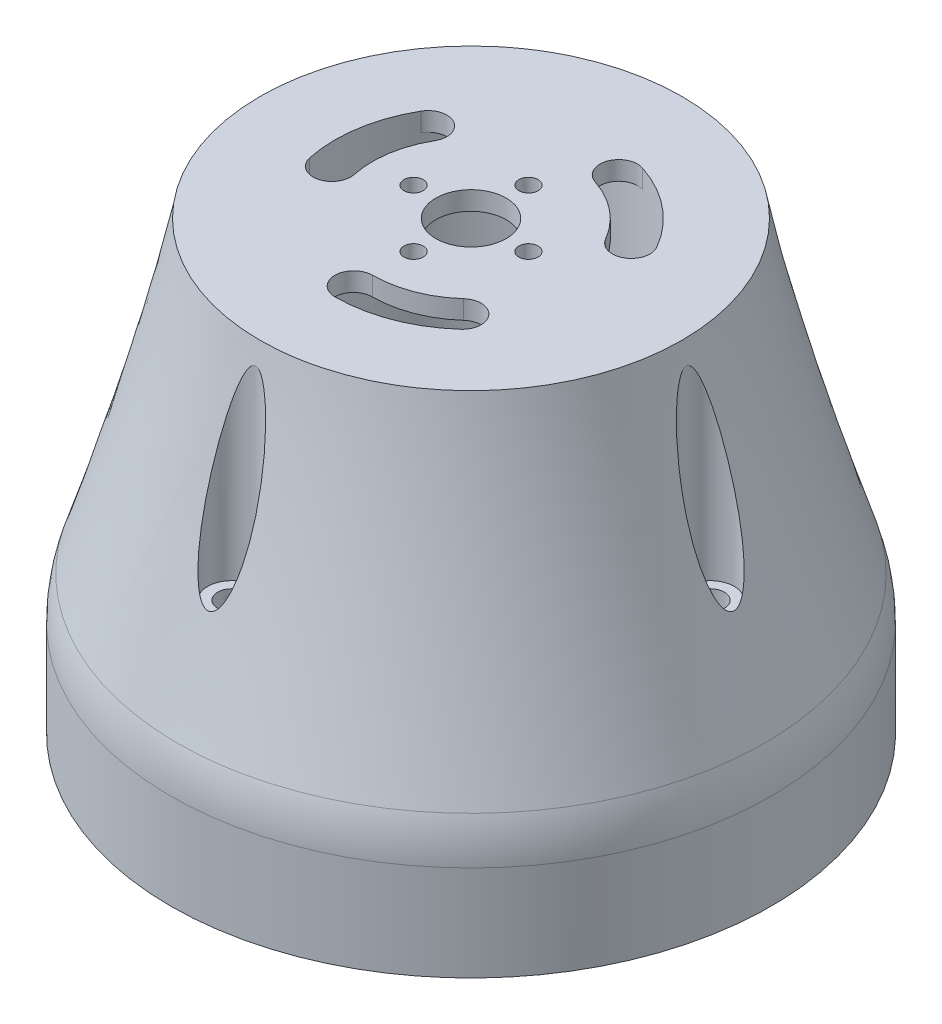
SolidWorks part; units mm, degrees
ref_plane "Front Plane" through (0, 0, 0) normal (0, 0, 1) x (1, 0, 0)
ref_plane "Top Plane" through (0, 0, 0) normal (0, 1, 0) x (1, 0, 0)
ref_plane "Right Plane" through (0, 0, 0) normal (1, 0, 0) x (0, 0, -1)
sketch "Sketch3" plane through (0, 0, 0) normal (0, 1, 0) x (1, 0, 0)
  circle A0 centre (0, 0) radius 64
  dimension "D1" = 128
extrude "Boss-Extrude1" add sketch "Sketch3" along normal blind 15
ref_plane "Plane1" through (0, 85, 0) normal (0, 1, 0) x (1, 0, 0)
sketch "Sketch4" plane through (0, 85, 0) normal (0, 1, 0) x (1, 0, 0)
  circle A0 centre (0, 0) radius 45
  dimension "D1" = 90
sketch "Sketch5" plane through (0, 15, 0) normal (0, 1, 0) x (1, 0, 0)
  circle A1 centre (0, 0) radius 64
  circle A2 centre (0, 0) radius 64
  dimension "D1" = 0
loft "Loft1" add profiles "Sketch5", "Sketch4" connector at (-2.5729, 15, 63.9483) connector at (15.8799, 85, 42.105)
fillet "Fillet1" radius 30 1 edges at (0, 15, 64) type face fillet first side face at (0, 15, 64) second side face at (0, 15, 64)
sketch "Sketch6" plane through (0, 85, 0) normal (0, 1, 0) x (1, 0, 0)
  circle A0 centre (0, 0) radius 51 construction
  circle A1 centre (0, 51) radius 3
  circle A2 centre (51, 0) radius 3
  circle A3 centre (0, -51) radius 3
  circle A4 centre (-51, 0) radius 3
  point P14 (0, 0)
  dimension "D1" = 102
  dimension "D2" = 6
  dimension "D3" = 4
extrude "Cut-Extrude1" cut sketch "Sketch6" against normal blind 85
sketch "Sketch8" plane through (0, 85, 0) normal (0, 1, 0) x (1, 0, 0)
  circle A0 centre (-51, 0) radius 5.11
  circle A1 centre (0, 51) radius 5.11
  circle A2 centre (51, 0) radius 5.11
  circle A3 centre (0, -51) radius 5.11
  point P12 (0, 0)
  dimension "D1" = 10.22
  dimension "D2" = 4
extrude "Cut-Extrude3" cut sketch "Sketch8" against normal blind 45
sketch "Sketch9" plane through (0, 0, 0) normal (0, -1, 0) x (1, 0, 0)
  arc A0 (-16.4684, 53.5238) -> (-53.5238, 16.4684) centre (0, 0) ccw
  arc A1 (-7.1314, 48.6777) -> (7.1314, 48.6777) centre (0, 51) ccw
  arc A5 (-7.1314, 48.6777) -> (-16.4684, 53.5238) centre (-14.2628, 46.3554) ccw
  arc A6 (16.4684, 53.5238) -> (7.1314, 48.6777) centre (14.2628, 46.3554) ccw
  arc A7 (48.6777, 7.1314) -> (53.5238, 16.4684) centre (46.3554, 14.2628) ccw
  arc A8 (48.6777, 7.1314) -> (48.6777, -7.1314) centre (51, 0) ccw
  arc A9 (53.5238, -16.4684) -> (48.6777, -7.1314) centre (46.3554, -14.2628) ccw
  arc A10 (7.1314, -48.6777) -> (16.4684, -53.5238) centre (14.2628, -46.3554) ccw
  arc A11 (7.1314, -48.6777) -> (-7.1314, -48.6777) centre (0, -51) ccw
  arc A12 (-16.4684, -53.5238) -> (-7.1314, -48.6777) centre (-14.2628, -46.3554) ccw
  arc A13 (-48.6777, -7.1314) -> (-53.5238, -16.4684) centre (-46.3554, -14.2628) ccw
  arc A14 (-48.6777, -7.1314) -> (-48.6777, 7.1314) centre (-51, 0) ccw
  arc A15 (-53.5238, 16.4684) -> (-48.6777, 7.1314) centre (-46.3554, 14.2628) ccw
  arc A16 (53.5238, 16.4684) -> (16.4684, 53.5238) centre (0, 0) ccw
  arc A17 (16.4684, -53.5238) -> (53.5238, -16.4684) centre (0, 0) ccw
  arc A18 (-53.5238, -16.4684) -> (-16.4684, -53.5238) centre (0, 0) ccw
  point P15 (0, 0)
  point P35 (0, 0)
  dimension "D1" = 112
  dimension "D2" = 15
  dimension "D3" = 4
  dimension "D4" = 15
  dimension "D5" = 15
extrude "Cut-Extrude4" cut sketch "Sketch9" against normal blind 12
sketch "Sketch17" plane through (0, 12, 0) normal (0, -1, 0) x (1, 0, 0)
  circle A0 centre (0, 0) radius 29
  dimension "D1" = 58
extrude "Cut-Extrude10" cut sketch "Sketch17" against normal blind 69
sketch "Sketch19" plane through (0, 0, 0) normal (0, -1, 0) x (1, 0, 0)
  arc A0 (16.4684, -53.5238) -> (53.5238, -16.4684) centre (0, 0) ccw construction
  circle A1 centre (0, 0) radius 64
  circle A2 centre (0, 0) radius 64
  arc A3 (53.5238, -16.4684) -> (48.6777, -7.1314) centre (46.3554, -14.2628) ccw construction
  arc A4 (48.6777, 7.1314) -> (48.6777, -7.1314) centre (51, 0) ccw construction
  arc A5 (48.6777, 7.1314) -> (53.5238, 16.4684) centre (46.3554, 14.2628) ccw construction
  arc A6 (53.5238, 16.4684) -> (16.4684, 53.5238) centre (0, 0) ccw construction
  arc A7 (-7.1314, 48.6777) -> (7.1314, 48.6777) centre (0, 51) ccw construction
  arc A8 (-7.1314, 48.6777) -> (-16.4684, 53.5238) centre (-14.2628, 46.3554) ccw construction
  arc A9 (16.4684, -53.5238) -> (53.5238, -16.4684) centre (0, 0) ccw
  arc A10 (53.5238, -16.4684) -> (48.6777, -7.1314) centre (46.3554, -14.2628) ccw
  arc A11 (48.6777, 7.1314) -> (48.6777, -7.1314) centre (51, 0) ccw
  arc A12 (48.6777, 7.1314) -> (53.5238, 16.4684) centre (46.3554, 14.2628) ccw
  arc A13 (53.5238, 16.4684) -> (16.4684, 53.5238) centre (0, 0) ccw
  arc A14 (-7.1314, 48.6777) -> (7.1314, 48.6777) centre (0, 51) ccw
  arc A15 (-7.1314, 48.6777) -> (-16.4684, 53.5238) centre (-14.2628, 46.3554) ccw
  arc A18 (16.4684, 53.5238) -> (7.1314, 48.6777) centre (14.2628, 46.3554) ccw
  arc A19 (-7.1314, 48.6777) -> (7.1314, 48.6777) centre (0, 51) ccw
  arc A20 (-7.1314, 48.6777) -> (-16.4684, 53.5238) centre (-14.2628, 46.3554) ccw
  arc A21 (-16.4684, 53.5238) -> (-53.5238, 16.4684) centre (0, 0) ccw
  arc A22 (-53.5238, 16.4684) -> (-48.6777, 7.1314) centre (-46.3554, 14.2628) ccw
  arc A23 (-48.6777, -7.1314) -> (-48.6777, 7.1314) centre (-51, 0) ccw
  arc A24 (-48.6777, -7.1314) -> (-53.5238, -16.4684) centre (-46.3554, -14.2628) ccw
  arc A25 (-53.5238, -16.4684) -> (-16.4684, -53.5238) centre (0, 0) ccw
  arc A26 (-16.4684, -53.5238) -> (-7.1314, -48.6777) centre (-14.2628, -46.3554) ccw
  arc A27 (7.1314, -48.6777) -> (-7.1314, -48.6777) centre (0, -51) ccw
  arc A28 (7.1314, -48.6777) -> (16.4684, -53.5238) centre (14.2628, -46.3554) ccw
  arc A29 (16.4684, -53.5238) -> (53.5238, -16.4684) centre (0, 0) ccw
  arc A30 (53.5238, -16.4684) -> (48.6777, -7.1314) centre (46.3554, -14.2628) ccw
  arc A31 (48.6777, 7.1314) -> (48.6777, -7.1314) centre (51, 0) ccw
  arc A32 (48.6777, 7.1314) -> (53.5238, 16.4684) centre (46.3554, 14.2628) ccw
  arc A33 (53.5238, 16.4684) -> (16.4684, 53.5238) centre (0, 0) ccw
  arc A34 (16.4684, 53.5238) -> (7.1314, 48.6777) centre (14.2628, 46.3554) ccw
  arc A35 (-7.1314, 48.6777) -> (7.1314, 48.6777) centre (0, 51) ccw
  arc A36 (-7.1314, 48.6777) -> (-16.4684, 53.5238) centre (-14.2628, 46.3554) ccw
  arc A37 (-16.4684, 53.5238) -> (-53.5238, 16.4684) centre (0, 0) ccw
  arc A38 (-53.5238, 16.4684) -> (-48.6777, 7.1314) centre (-46.3554, 14.2628) ccw
  arc A39 (-48.6777, -7.1314) -> (-48.6777, 7.1314) centre (-51, 0) ccw
  arc A40 (-48.6777, -7.1314) -> (-53.5238, -16.4684) centre (-46.3554, -14.2628) ccw
  arc A41 (-53.5238, -16.4684) -> (-16.4684, -53.5238) centre (0, 0) ccw
  arc A42 (-16.4684, -53.5238) -> (-7.1314, -48.6777) centre (-14.2628, -46.3554) ccw
  arc A43 (7.1314, -48.6777) -> (-7.1314, -48.6777) centre (0, -51) ccw
  arc A44 (7.1314, -48.6777) -> (16.4684, -53.5238) centre (14.2628, -46.3554) ccw
  arc A45 (16.4684, -53.5238) -> (53.5238, -16.4684) centre (0, 0) ccw
  arc A46 (53.5238, -16.4684) -> (48.6777, -7.1314) centre (46.3554, -14.2628) ccw
  arc A47 (48.6777, 7.1314) -> (48.6777, -7.1314) centre (51, 0) ccw
  arc A48 (48.6777, 7.1314) -> (53.5238, 16.4684) centre (46.3554, 14.2628) ccw
  arc A49 (53.5238, 16.4684) -> (16.4684, 53.5238) centre (0, 0) ccw
  circle M19 centre (0, -51) radius 3
  circle M20 centre (51, 0) radius 3
  circle M21 centre (0, 51) radius 3
  circle M22 centre (-51, 0) radius 3
  circle M23 centre (0, 0) radius 64
  arc M24 (-7.1314, 48.6777) -> (7.1314, 48.6777) centre (0, 51) ccw
  arc M25 (7.1314, 48.6777) -> (16.4684, 53.5238) centre (14.2628, 46.3554) cw
  arc M26 (16.4684, 53.5238) -> (53.5238, 16.4684) centre (0, 0) cw
  arc M27 (53.5238, 16.4684) -> (48.6777, 7.1314) centre (46.3554, 14.2628) cw
  arc M28 (48.6777, 7.1314) -> (48.6777, -7.1314) centre (51, 0) ccw
  arc M29 (48.6777, -7.1314) -> (53.5238, -16.4684) centre (46.3554, -14.2628) cw
  arc M30 (53.5238, -16.4684) -> (16.4684, -53.5238) centre (0, 0) cw
  arc M31 (16.4684, -53.5238) -> (7.1314, -48.6777) centre (14.2628, -46.3554) cw
  arc M32 (7.1314, -48.6777) -> (-7.1314, -48.6777) centre (0, -51) ccw
  arc M33 (-7.1314, -48.6777) -> (-16.4684, -53.5238) centre (-14.2628, -46.3554) cw
  arc M34 (-16.4684, -53.5238) -> (-53.5238, -16.4684) centre (0, 0) cw
  arc M35 (-53.5238, -16.4684) -> (-48.6777, -7.1314) centre (-46.3554, -14.2628) cw
  arc M36 (-48.6777, -7.1314) -> (-48.6777, 7.1314) centre (-51, 0) ccw
  arc M37 (-48.6777, 7.1314) -> (-53.5238, 16.4684) centre (-46.3554, 14.2628) cw
  arc M38 (-53.5238, 16.4684) -> (-16.4684, 53.5238) centre (0, 0) cw
  arc M39 (-16.4684, 53.5238) -> (-7.1314, 48.6777) centre (-14.2628, 46.3554) cw
  dimension "D1" = 0
  dimension "D2" = 0
extrude "Boss-Extrude3" add sketch "Sketch19" along normal blind 10 contours M23 M20 M22 M39 M24 M25 M26 M27 M28 M29 M30 M31 M32 M33 M34 M35 M36 M37 M38 M21 M19 region at (-62.1898, 0, 0)
sketch "Sketch20" plane through (0, 85, 0) normal (0, 1, 0) x (1, 0, 0)
  circle A0 centre (0, 0) radius 12.25 construction
  circle A1 centre (0, 0) radius 7.5
  circle A2 centre (0, 12.25) radius 2.05
  circle A3 centre (12.25, 0) radius 2.05
  circle A4 centre (0, -12.25) radius 2.05
  circle A5 centre (-12.25, 0) radius 2.05
  point P15 (0, 0)
  dimension "D1" = 24.5
  dimension "D2" = 15
  dimension "D3" = 4.1
  dimension "D4" = 4
extrude "Cut-Extrude12" cut sketch "Sketch20" against normal blind 10
sketch "Sketch25" plane through (0, 85, 0) normal (0, 1, 0) x (1, 0, 0)
  circle A0 centre (0, 0) radius 25 construction
  arc A1 (16.7295, -18.5775) -> (0, -25) centre (0, 0) cw construction
  arc A2 (0, -29) -> (19.4062, -21.5499) centre (0, 0) ccw
  arc A3 (0, -21) -> (14.0528, -15.6051) centre (0, 0) ccw
  arc A4 (0, -21) -> (0, -29) centre (0, -25) ccw
  arc A5 (19.4062, -21.5499) -> (14.0528, -15.6051) centre (16.7295, -18.5775) ccw
  arc A6 (-24.4533, -5.1994) -> (-21.6506, 12.5) centre (0, 0) cw construction
  arc A7 (-25.1147, 14.5) -> (-28.3659, -6.0313) centre (0, 0) ccw
  arc A8 (-18.1865, 10.5) -> (-20.5408, -4.3675) centre (0, 0) ccw
  arc A9 (-18.1865, 10.5) -> (-25.1147, 14.5) centre (-21.6506, 12.5) ccw
  arc A10 (-28.3659, -6.0313) -> (-20.5408, -4.3675) centre (-24.4533, -5.1994) ccw
  arc A11 (7.7239, 23.7769) -> (21.6506, 12.5) centre (0, 0) cw construction
  arc A12 (25.1147, 14.5) -> (8.9597, 27.5812) centre (0, 0) ccw
  arc A13 (18.1865, 10.5) -> (6.488, 19.9726) centre (0, 0) ccw
  arc A14 (18.1865, 10.5) -> (25.1147, 14.5) centre (21.6506, 12.5) ccw
  arc A15 (8.9597, 27.5812) -> (6.488, 19.9726) centre (7.7239, 23.7769) ccw
  point P5 (8.96, -23.3392)
  point P14 (-24.6923, 3.91)
  point P21 (15.7324, 19.4292)
  point P26 (0, 0)
  dimension "D1" = 50
  dimension "D2" = 4
  dimension "D5" = 3
extrude "Cut-Extrude16" cut sketch "Sketch25" against normal blind 5
